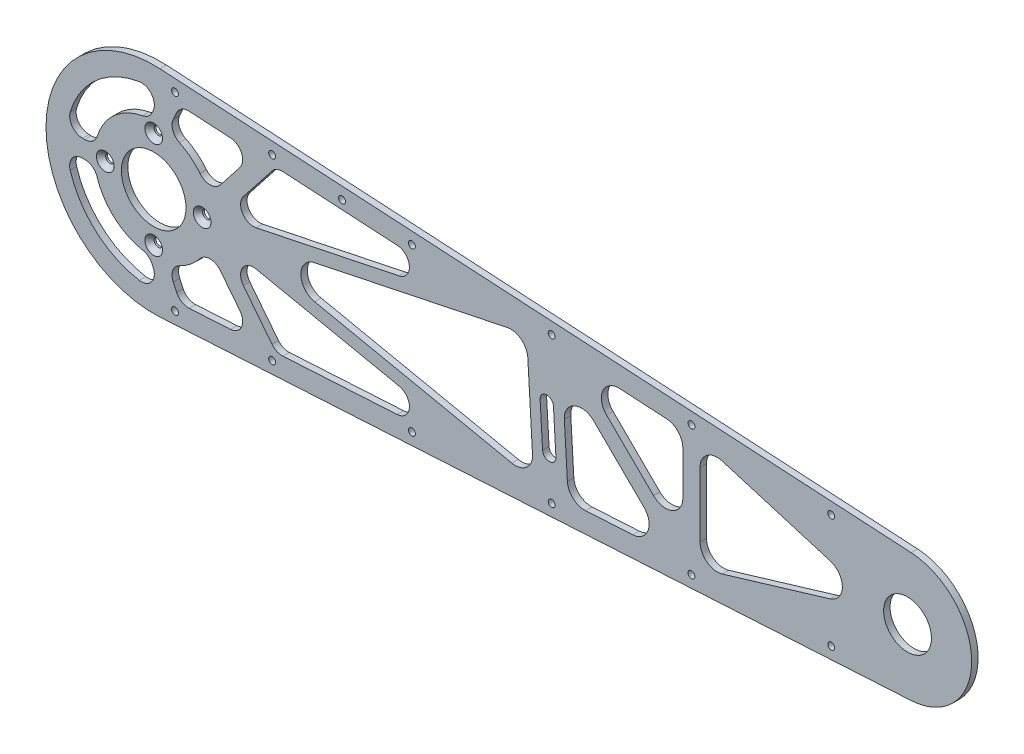
SolidWorks part; units mm, degrees
material "Thornel VCB-20 Carbon Cloth"
ref_plane "Front Plane" through (0, 0, 0) normal (0, 0, 1) x (1, 0, 0)
ref_plane "Top Plane" through (0, 0, 0) normal (0, 1, 0) x (1, 0, 0)
ref_plane "Right Plane" through (0, 0, 0) normal (1, 0, 0) x (0, 0, -1)
sketch "Sketch1" plane through (0, 0, 0) normal (0, 0, 1) x (1, 0, 0)
  line L0 (-175, 0) -> (175, 0) construction
  line L1 (-172.1122, 49.9165) -> (176.7203, 29.7354)
  line L2 (-172.1122, -49.9165) -> (176.7203, -29.7354)
  line L3 (139.566, 26.3757) -> (-120, 41.3925) construction
  line L4 (-55.1085, -37.6383) -> (9.783, -33.8841) construction
  line L5 (-125, 0) -> (-125, 62.9978) construction
  line L6 (-55.5713, 29.6383) -> (-120.4628, 33.3925) construction
  line L7 (-120.4628, 33.3925) -> (-120, 41.3925) construction
  line L8 (-55.5713, 29.6383) -> (-55.1085, 37.6383) construction
  line L9 (-88.0171, 31.5154) -> (-87.5543, 39.5154) construction
  line L10 (-120, -41.3925) -> (-165.1122, -44.0024) construction
  circle A0 centre (175, 0) radius 11.1125
  arc A1 (176.7203, 29.7354) -> (176.7203, -29.7354) centre (175, 0) cw
  circle A3 centre (-175, 0) radius 22.5 construction
  circle A7 centre (-175, 0) radius 15
  circle A9 centre (-120, 41.3925) radius 1.6
  circle A10 centre (-55.1085, 37.6383) radius 1.6
  circle A11 centre (9.783, 33.8841) radius 1.6
  circle A12 centre (74.6745, 30.1299) radius 1.6
  circle A13 centre (139.566, 26.3757) radius 1.6
  circle A15 centre (139.566, -26.3757) radius 1.6
  circle A16 centre (74.6745, -30.1299) radius 1.6
  circle A17 centre (9.783, -33.8841) radius 1.6
  circle A18 centre (-55.1085, -37.6383) radius 1.6
  circle A19 centre (-120, -41.3925) radius 1.6
  arc A20 (-172.1122, 49.9165) -> (-172.1122, -49.9165) centre (-175, 0) ccw
  circle A21 centre (-87.5543, 39.5154) radius 1.6
  circle A22 centre (-165.1122, -44.0024) radius 1.6
  circle A23 centre (-165.1122, 44.0024) radius 1.6
  point P4 (0, 0)
  point P18 (-175, 22.5)
  point P21 (-197.5, 0)
  point P22 (-175, -22.5)
  point P23 (-152.5, 0)
  point P30 (-88.0171, 31.5154)
  dimension "D2" = 22.225
  dimension "D3" = 50
  dimension "D5" = 45
  dimension "D6" = 3.2
  dimension "D7" = 260
  dimension "D8" = 5
  dimension "D9" = 7
  dimension "D10" = 30
  dimension "D16" = 5
  dimension "D1" = 350
  dimension "D4" = 8
  dimension "D12" = 5.5
extrude "Boss-Extrude1" add sketch "Sketch1" along normal blind 3
sketch "Sketch4" plane through (0, 0, 3) normal (0, 0, 1) x (1, 0, 0)
  point P10 (-197.5, 0)
  point P13 (-175, 22.5)
  point P16 (-152.5, 0)
  point P19 (-175, -22.5)
hole_wizard "CSK for M3.5 Flat Head Machine Screw1" positions "Sketch4" profile "Sketch6" countersink size "M3.5" standard "ANSI Metric" end condition up to next
sketch "Sketch6" plane through (-197.5, 0, 3) normal (1, 0, 0) x (0, -1, 0)
  line L0 (0, 0) -> (0, 3)
  line L1 (0, 3) -> (1.95, 3)
  line L2 (1.95, 3) -> (1.95, 2.15)
  line L3 (1.95, 2.15) -> (4.1, 0)
  line L5 (4.1, 0) -> (0, 0)
  line L6 (-1.95, 2.15) -> (-4.1, 0) construction
  line L11 (0, -6.35) -> (0, 107.95) construction
  dimension "Thru Hole Dia." = 3.9
  dimension "Thru Hole Depth" = 3
  dimension "Near C'Sink Dia." = 8.2
  dimension "Near C'Sink Angle" = 90
sketch "Sketch7" plane through (0, 0, 3) normal (0, 0, 1) x (1, 0, 0)
  line L0 (74.6745, 30.1299) -> (74.6745, -30.1299) construction
  line L1 (74.6745, -30.1299) -> (175, 0) construction
  line L2 (175, 0) -> (74.6745, 30.1299) construction
  line L3 (175, 0) -> (-152.5, 0) construction
  line L4 (175, -29.8349) -> (175, 29.8349) construction
  line L5 (88.9755, 22.7026) -> (139.0575, 7.6619)
  line L6 (139.0575, -7.6619) -> (88.9755, -22.7026)
  line L7 (78.6745, -15.0407) -> (78.6745, 15.0407)
  line L8 (9.783, -33.8841) -> (5.5294, 39.6394) construction
  line L9 (9.783, 33.8841) -> (74.6745, -30.1299) construction
  line L10 (9.783, 33.8841) -> (74.6745, 30.1299) construction
  line L11 (9.783, -33.8841) -> (74.6745, -30.1299) construction
  line L12 (-152.5, 0) -> (-55.1085, 37.6383) construction
  line L13 (-55.1085, 37.6383) -> (9.783, 33.8841) construction
  line L14 (9.783, 33.8841) -> (-152.5, 0) construction
  line L15 (70.6745, -1.436) -> (70.6745, 18.8041)
  line L16 (63.1365, 26.7907) -> (41.3408, 28.0517)
  line L17 (35.2605, 14.3698) -> (57.0563, -7.1312)
  line L18 (29.2743, 9.0376) -> (52.6422, -14.0143)
  line L19 (47.486, -27.6962) -> (25.5253, -28.9667)
  line L20 (17.0766, -21.4421) -> (15.6694, 2.8804)
  line L21 (176.7203, 29.7354) -> (-172.1122, 49.9165) construction
  line L22 (-172.1122, -49.9165) -> (176.7203, -29.7354) construction
  line L23 (0.8889, -18.6602) -> (-1.2973, 19.1278)
  line L24 (-10.9191, 26.4969) -> (-100.3161, 7.8311)
  line L25 (-100.3161, -7.8311) -> (-8.7329, -26.9534)
  line L35 (-197.5, 0) -> (-55.1085, 37.6383) construction
  line L52 (-55.1085, -37.6383) -> (-175, -22.5) construction
  line L53 (-15.2425, -47.7117) -> (-52.5586, -43) construction
  line L54 (-0.7058, -39.4678) -> (2.1851, -39.8329) construction
  line L55 (8.6627, -14.5198) -> (7.5076, 5.4468) construction
  line L56 (5.5679, -14.6989) -> (4.4127, 5.2678)
  line L57 (11.7575, -14.3408) -> (10.6024, 5.6258)
  line L58 (176.7203, 29.7354) -> (-172.1122, 49.9165) construction
  line L59 (-175, 22.5) -> (-165.1122, 44.0024) construction
  line L60 (-152.5, 0) -> (-120, 41.3925) construction
  line L61 (-133.3776, 17.8775) -> (-120.0806, 34.8127)
  line L62 (-115.0148, 37.0974) -> (-61.9156, 34.0254)
  line L63 (-61.0358, 22.1621) -> (-127.4321, 8.2988)
  line L64 (-165.9126, 32.6875) -> (-164.3288, 36.1317)
  line L65 (-158.531, 39.6149) -> (-139.3382, 38.5046)
  line L66 (-134.9656, 28.8093) -> (-144.0924, 17.1852)
  line L67 (-175.7645, 30.4115) -> (-175.2558, 31.5179)
  line L68 (-197.5, 0) -> (-225, 0) construction
  line L69 (-208.0189, 4) -> (-206.9726, 4)
  line L70 (-208.0189, -4) -> (-206.9726, -4)
  line L71 (-175.7645, -30.4115) -> (-175.2558, -31.5179)
  line L72 (-165.9126, -32.6875) -> (-164.3288, -36.1317)
  line L73 (-158.531, -39.6149) -> (-139.3382, -38.5046)
  line L74 (-134.9656, -28.8093) -> (-144.0924, -17.1852)
  line L75 (-115.0148, -37.0974) -> (-61.9156, -34.0254)
  line L76 (-133.3776, -17.8775) -> (-120.0806, -34.8127)
  line L77 (-61.0358, -22.1621) -> (-127.4321, -8.2988)
  arc A0 (139.0575, 7.6619) -> (139.0575, -7.6619) centre (136.7565, 0) cw
  arc A1 (88.9755, -22.7026) -> (78.6745, -15.0407) centre (86.6745, -15.0407) cw
  arc A2 (88.9755, 22.7026) -> (78.6745, 15.0407) centre (86.6745, 15.0407) ccw
  arc A3 (70.6745, 18.8041) -> (63.1365, 26.7907) centre (62.6745, 18.8041) ccw
  arc A4 (41.3408, 28.0517) -> (35.2605, 14.3698) centre (40.8787, 20.065) ccw
  arc A5 (70.6745, -1.436) -> (57.0563, -7.1312) centre (62.6745, -1.436) cw
  arc A6 (52.6422, -14.0143) -> (47.486, -27.6962) centre (47.024, -19.7095) cw
  arc A7 (25.5253, -28.9667) -> (17.0766, -21.4421) centre (25.0632, -20.98) cw
  arc A8 (29.2743, 9.0376) -> (15.6694, 2.8804) centre (23.6561, 3.3424) ccw
  arc A9 (0.8889, -18.6602) -> (-8.7329, -26.9534) centre (-7.0978, -19.1222) cw
  arc A10 (-1.2973, 19.1278) -> (-10.9191, 26.4969) centre (-9.2839, 18.6658) ccw
  arc A11 (-100.3161, 7.8311) -> (-100.3161, -7.8311) centre (-98.681, 0) ccw
  circle A30 centre (-175, 0) radius 15 construction
  circle A31 centre (-175, 0) radius 15 construction
  circle A32 centre (-175, 0) radius 22.5 construction
  circle A49 centre (9.783, -33.8841) radius 1.6 construction
  circle A50 centre (9.783, -33.8841) radius 1.6
  circle A52 centre (175, 0) radius 11.1125 construction
  circle A53 centre (175, 0) radius 11.1125 construction
  arc A56 (5.5679, -14.6989) -> (11.7575, -14.3408) centre (8.6627, -14.5198) ccw
  arc A57 (10.6024, 5.6258) -> (4.4127, 5.2678) centre (7.5076, 5.4468) ccw
  circle A58 centre (-165.1122, 44.0024) radius 1.6 construction
  circle A60 centre (-120, 41.3925) radius 1.6 construction
  arc A61 (-153.502, 17.149) -> (-163.0653, 24.7753) centre (-175, 0) ccw
  arc A62 (-180.1025, 27.0225) -> (-201.2462, 8.209) centre (-175, 0) ccw
  arc A63 (-181.6995, 39.942) -> (-213.7614, 11.7391) centre (-175, 0) ccw
  arc A64 (-172.1122, 49.9165) -> (-172.1122, -49.9165) centre (-175, 0) ccw construction
  arc A65 (-175.2558, 31.5179) -> (-181.6995, 39.942) centre (-180.707, 34.0247) ccw
  arc A66 (-213.7614, 11.7391) -> (-208.0189, 4) centre (-208.0189, 10) ccw
  arc A67 (-201.2462, 8.209) -> (-206.9726, 4) centre (-206.9726, 10) cw
  arc A68 (-180.1025, 27.0225) -> (-175.7645, 30.4115) centre (-181.2158, 32.9183) ccw
  arc A69 (-61.9156, 34.0254) -> (-61.0358, 22.1621) centre (-62.2621, 28.0354) cw
  arc A70 (-120.0806, 34.8127) -> (-115.0148, 37.0974) centre (-115.3614, 31.1074) cw
  arc A71 (-133.3776, 17.8775) -> (-127.4321, 8.2988) centre (-128.6584, 14.1721) ccw
  arc A72 (-139.3382, 38.5046) -> (-134.9656, 28.8093) centre (-139.6847, 32.5146) cw
  arc A73 (-164.3288, 36.1317) -> (-158.531, 39.6149) centre (-158.8776, 33.625) cw
  arc A74 (-163.0653, 24.7753) -> (-165.9126, 32.6875) centre (-160.4614, 30.1808) cw
  arc A75 (-153.502, 17.149) -> (-144.0924, 17.1852) centre (-148.8115, 20.8905) ccw
  arc A76 (-213.7614, -11.7391) -> (-208.0189, -4) centre (-208.0189, -10) cw
  arc A77 (-201.2462, -8.209) -> (-206.9726, -4) centre (-206.9726, -10) ccw
  arc A78 (-180.1025, -27.0225) -> (-201.2462, -8.209) centre (-175, 0) cw
  arc A79 (-181.6995, -39.942) -> (-213.7614, -11.7391) centre (-175, 0) cw
  arc A80 (-180.1025, -27.0225) -> (-175.7645, -30.4115) centre (-181.2158, -32.9183) cw
  arc A81 (-175.2558, -31.5179) -> (-181.6995, -39.942) centre (-180.707, -34.0247) cw
  arc A82 (-164.3288, -36.1317) -> (-158.531, -39.6149) centre (-158.8776, -33.625) ccw
  arc A83 (-163.0653, -24.7753) -> (-165.9126, -32.6875) centre (-160.4614, -30.1808) ccw
  arc A84 (-153.502, -17.149) -> (-163.0653, -24.7753) centre (-175, 0) cw
  arc A85 (-153.502, -17.149) -> (-144.0924, -17.1852) centre (-148.8115, -20.8905) cw
  arc A86 (-139.3382, -38.5046) -> (-134.9656, -28.8093) centre (-139.6847, -32.5146) ccw
  arc A87 (-61.9156, -34.0254) -> (-61.0358, -22.1621) centre (-62.2621, -28.0354) ccw
  arc A88 (-120.0806, -34.8127) -> (-115.0148, -37.0974) centre (-115.3614, -31.1074) ccw
  arc A89 (-133.3776, -17.8775) -> (-127.4321, -8.2988) centre (-128.6584, -14.1721) cw
  point P36 (164.5699, 0)
  point P59 (-137.8221, 0)
  point P102 (-15.2425, -47.7117)
  point P126 (8.0851, -4.5365)
  dimension "D8" = 8
  dimension "D11" = 27.5
  dimension "D12" = 5
  dimension "D20" = 3.1
  dimension "D10" = 4
  dimension "D17" = 6
  dimension "D1" = 3
  dimension "D3" = 8
  dimension "D4" = 8
  dimension "D5" = 8
  dimension "D6" = 16
  dimension "D7" = 6
  dimension "D9" = 8
  dimension "D13" = 8
  dimension "D14" = 5
  dimension "D15" = 8
  dimension "D16" = 24.8967
  dimension "D22" = 20
extrude "Cut-Extrude1" cut sketch "Sketch7" against normal blind 10 contours L57 A57 L56 A56 | L24 A11 L25 A9 L23 A10 | L18 A8 L20 A7 L19 A6 | L61 A71 L63 A69 L62 A70 | A61 A75 L66 A72 L65 A73 L64 A74 | A62 A68 L67 A65 A63 A66 L69 A67 | L20 A8 L18 A6 L19 A7 | L17 A5 L15 A3 L16 A4 | L7 A2 L5 A0 L6 A1 | L75 A87 L77 A89 L76 A88 | L73 A86 L74 A85 A84 A83 L72 A82 | A81 A79 A76 L70 A77 A78 A80 L71 region at (32.1755, -11.823, 3) region at (-42.4165, -0.2065, 3) region at (8.0851, -4.5365, 3) region at (-98.5963, 24.3683, 3) region at (-150.0822, 29.1724, 3) region at (-195.9659, 23.7676, 3)
sketch "Sketch9" [suppressed] plane through (0, 0, 3) normal (0, 0, 1) x (1, 0, 0)
  line L2 (176.7203, 29.7354) -> (-172.1122, 49.9165) construction
  line L3 (-172.1122, -49.9165) -> (176.7203, -29.7354) construction
  line L4 (254.5375, 0) -> (208, 0) construction
  line L5 (200.557, 2) -> (203.931, 2)
  line L6 (200.557, -2) -> (203.931, -2)
  line L7 (162.9445, 26.3755) -> (155.7345, 26.7926)
  line L8 (162.9445, -26.3755) -> (155.7345, -26.7926)
  arc A1 (155.7345, -26.7926) -> (155.7345, 26.7926) centre (175, 0) ccw
  arc A2 (176.7203, -29.7354) -> (176.7203, 29.7354) centre (175, 0) ccw construction
  arc A3 (200.557, -2) -> (200.557, 2) centre (175, 0) ccw
  arc A4 (162.9445, 26.3755) -> (203.931, 2) centre (175, 0) cw
  arc A5 (203.931, -2) -> (162.9445, -26.3755) centre (175, 0) cw
  dimension "D1" = 33
  dimension "D2" = 4
  dimension "D3" = 4
extrude "Boss-Extrude2" [suppressed] add sketch "Sketch9" against normal up to surface (3 mm away) up to face at (56.1489, 13.0862, 0)
fillet "Fillet1" [suppressed] radius 1
fillet "Fillet2" [suppressed] radius 80
